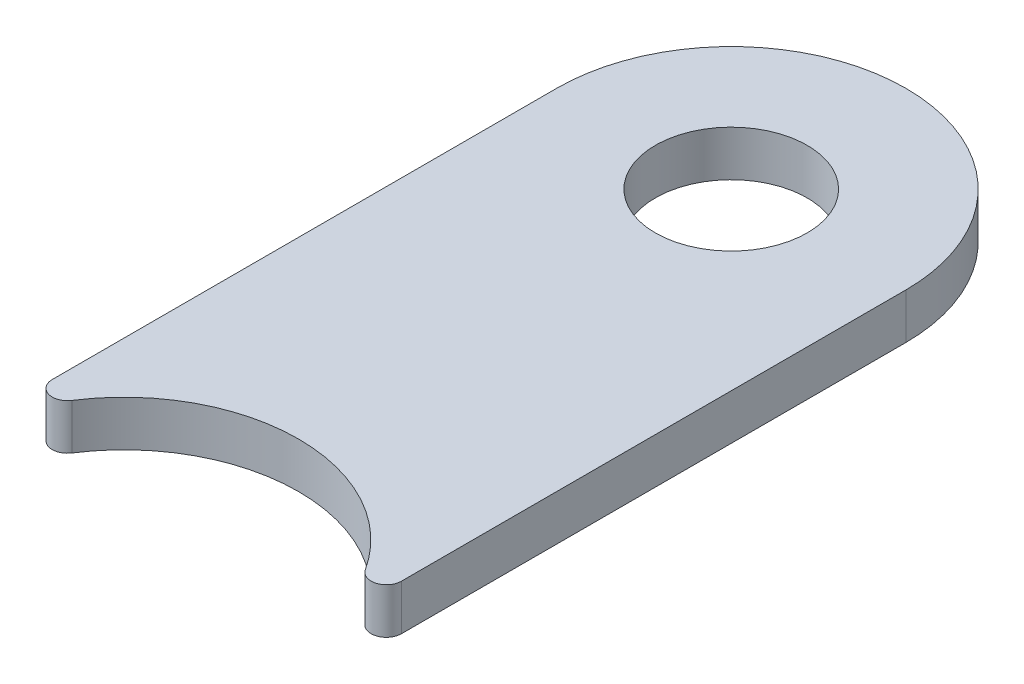
SolidWorks part; units mm, degrees
ref_plane "Front Plane" through (0, 0, 0) normal (0, 0, 1) x (1, 0, 0)
ref_plane "Top Plane" through (0, 0, 0) normal (0, 1, 0) x (1, 0, 0)
ref_plane "Right Plane" through (0, 0, 0) normal (1, 0, 0) x (0, 0, -1)
sketch "Sketch1" plane through (0, 0, 0) normal (0, 1, 0) x (1, 0, 0)
  line L0 (-11.5, 40) -> (-11.5, 0)
  line L1 (11.5, 40) -> (11.5, 0)
  line L2 (-11.5, 0) -> (11.5, 0)
  circle A0 centre (0, 0) radius 11.5
  circle A1 centre (0, 40) radius 11.5
  circle A2 centre (0, 40) radius 5
  dimension "D1" = 10
  dimension "D2" = 23
  dimension "D3" = 40
extrude "Boss-Extrude1" add sketch "Sketch1" along normal blind 3 contours A1 L0 A0 L1 | A1 A2 region at (0, 0, -20) region at (0, 0, -51.1747)
fillet "Fillet1" radius 1 2 edges at (-11.5, 1.5, 0) (11.5, 1.5, 0)
